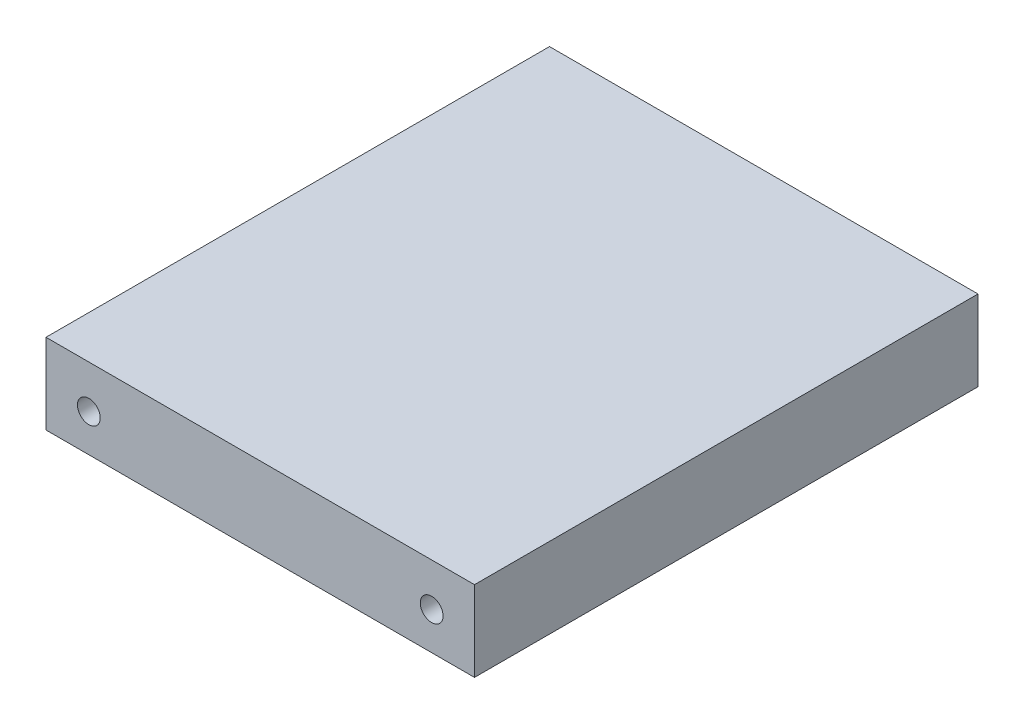
SolidWorks part; units mm, degrees
ref_plane "Front Plane" through (0, 0, 0) normal (0, 0, 1) x (1, 0, 0)
ref_plane "Top Plane" through (0, 0, 0) normal (0, 1, 0) x (1, 0, 0)
ref_plane "Right Plane" through (0, 0, 0) normal (1, 0, 0) x (0, 0, -1)
sketch "Sketch2" plane through (0, 0, 0) normal (0, 1, 0) x (1, 0, 0)
  line L1 (-25.4, 29.845) -> (25.4, 29.845)
  line L2 (-25.4, 29.845) -> (-25.4, -29.845)
  line L3 (-25.4, -29.845) -> (25.4, -29.845)
  line L4 (25.4, 29.845) -> (25.4, -29.845)
  line L5 (-25.4, 29.845) -> (25.4, -29.845) construction
  line L6 (-25.4, -29.845) -> (25.4, 29.845) construction
  point P0 (0, 0)
  dimension "D1" = 50.8
  dimension "D2" = 59.69
extrude "Boss-Extrude1" add sketch "Sketch2" along normal blind 9.525 contours L2 L3 L4 L1
sketch "Sketch3" plane through (0, 0, 29.845) normal (0, 0, 1) x (1, 0, 0)
  circle A0 centre (20.32, 4.445) radius 1.8415
  circle A1 centre (-20.32, 4.445) radius 1.8415
hole_wizard "#6-32 Tapped Hole1" positions "Sketch4" profile "Sketch5" tap size "#6-32" standard "ANSI Inch"
sketch "Sketch4" plane through (0, 0, 29.845) normal (0, 0, 1) x (1, 0, 0)
  point P0 (-20.32, 4.445)
  point P2 (20.32, 4.445)
sketch "Sketch5" plane through (-20.32, 4.445, 29.845) normal (1, 0, 0) x (0, -1, 0)
  line L0 (0, 0) -> (0, 10.2107)
  line L1 (0, 10.2107) -> (1.3525, 9.398)
  line L2 (1.3525, 9.398) -> (1.3525, 0)
  line L5 (1.3525, 0) -> (0, 0)
  line L10 (0, 10.2107) -> (-1.3526, 9.398) construction
  line L11 (0, -6.35) -> (0, 107.95) construction
  dimension "Tap Drill Dia." = 2.7051
  dimension "Tap Drill Depth" = 9.398
  dimension "Drill Angle" = 118
cosmetic thread "Hole Thread1" parameters "D1"=7.112, "D2"=3.5052
cosmetic thread "Hole Thread2" parameters "D1"=7.112, "D2"=3.5052
hole_wizard "#6-32 Tapped Hole2" positions "Sketch6" profile "Sketch7" tap size "#6-32" standard "ANSI Inch"
sketch "Sketch6" plane through (0, 0, -29.845) normal (0, 0, -1) x (-1, 0, 0)
  point P0 (-20.32, 4.445)
  point P2 (20.32, 4.445)
sketch "Sketch7" plane through (20.32, 4.445, -29.845) normal (1, 0, 0) x (0, 1, 0)
  line L0 (0, 0) -> (0, 10.2107)
  line L1 (0, 10.2107) -> (1.3525, 9.398)
  line L2 (1.3525, 9.398) -> (1.3525, 0)
  line L5 (1.3525, 0) -> (0, 0)
  line L10 (0, 10.2107) -> (-1.3525, 9.398) construction
  line L11 (0, -6.35) -> (0, 107.95) construction
  dimension "Tap Drill Dia." = 2.7051
  dimension "Tap Drill Depth" = 9.398
  dimension "Drill Angle" = 118
cosmetic thread "Hole Thread3" parameters "D1"=7.112, "D2"=3.5052
cosmetic thread "Hole Thread4" parameters "D1"=7.112, "D2"=3.5052
